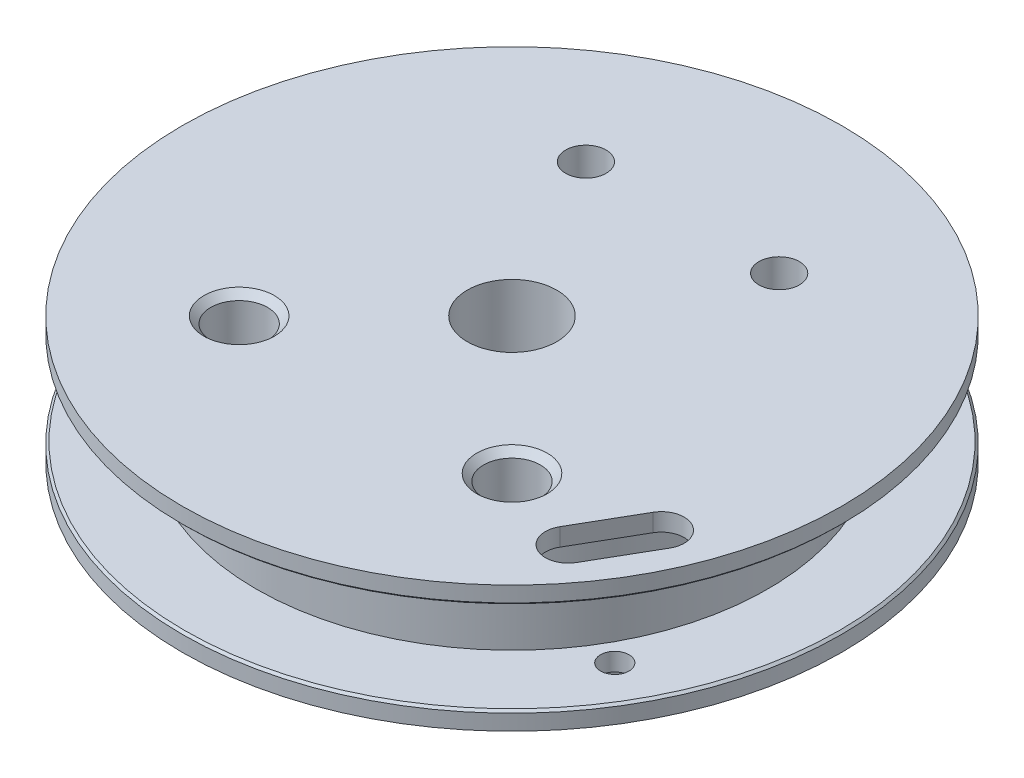
SolidWorks part; units mm, degrees
material "6061-T6 (SS)"
ref_plane "Front Plane" through (0, 0, 0) normal (0, 0, 1) x (1, 0, 0)
ref_plane "Top Plane" through (0, 0, 0) normal (0, 1, 0) x (1, 0, 0)
ref_plane "Right Plane" through (0, 0, 0) normal (1, 0, 0) x (0, 0, -1)
sketch "Sketch1" plane through (0, 0, 0) normal (0, 0, 1) x (1, 0, 0)
  line L0 (0, 0) -> (0, 83.8274) construction
  line L1 (-2.5, 22.994) -> (-9.525, 22.994)
  line L2 (-9.525, 22.994) -> (-9.525, 28.994)
  line L3 (-9.525, 28.994) -> (-18.415, 28.994)
  line L4 (-18.415, 28.994) -> (-18.415, 29.994)
  line L5 (-18.415, 29.994) -> (-14.2875, 29.994)
  line L6 (-14.2875, 29.994) -> (-14.2875, 35.074)
  line L7 (-14.2875, 35.074) -> (-2.5, 35.074) construction
  line L8 (-14.2875, 35.074) -> (-18.415, 35.074)
  line L9 (-2.5, 35.074) -> (-2.5, 22.994)
  line L10 (-18.415, 35.074) -> (-18.415, 36.0646)
  line L11 (-18.415, 36.0646) -> (-2.5, 36.0646)
  line L12 (-2.5, 36.0646) -> (-2.5, 35.074)
  dimension "D1" = 18.415
  dimension "D2" = 5.08
  dimension "D3" = 1
  dimension "D4" = 6
  dimension "D5" = 2.5
  dimension "D6" = 9.525
  dimension "D7" = 14.2875
  dimension "D8" = 0.9906
  dimension "D9" = 18.415
revolve "Revolve1" add sketch "Sketch1" angle 360 about L0
sketch "Sketch7" plane through (0, 29.994, 0) normal (0, 1, 0) x (1, 0, 0)
  line L0 (0, 0) -> (23.0958, 0) construction
  line L1 (0, 0) -> (19.9688, -11.529) construction
  circle A1 centre (0, 0) radius 15.6845 construction
  circle A4 centre (13.5832, -7.8423) radius 0.7938
  dimension "D1" = 30
  dimension "D2" = 31.369
  dimension "D4" = 1.5875
extrude "Cut-Extrude2" cut sketch "Sketch7" against normal blind 2.54 contours A4 region at (13.5832, 29.994, 7.8423)
sketch "Sketch8" plane through (0, 36.0646, 0) normal (0, 1, 0) x (1, 0, 0)
  line L1 (-26.9486, 0) -> (27.9762, 0) construction
  line L3 (-26.9486, -7.62) -> (27.9762, -7.62) construction
  line L4 (0, 11.7169) -> (0, -23.0173) construction
  circle A0 centre (7.62, -7.62) radius 1.5748
  circle A1 centre (-7.62, -7.62) radius 1.5748
  dimension "D3" = 3.1496
  dimension "D4" = 3.1496
  dimension "D1" = 7.62
  dimension "D2" = 7.62
  dimension "D5" = 7.62
hole_wizard "1/8 (0.125) Diameter Hole1" positions "Sketch10" profile "Sketch9" hole size "1/8" standard "ANSI Inch"
sketch "Sketch10" plane through (0, 36.0646, 0) normal (0, 1, 0) x (1, 0, 0)
  point P0 (-7.62, -7.62)
  point P3 (7.62, -7.62)
sketch "Sketch9" plane through (-7.62, 36.0646, 7.62) normal (1, 0, 0) x (0, 0, 1)
  line L0 (0, 0) -> (0, 6.0339)
  line L1 (0, 6.0339) -> (1.5875, 5.08)
  line L2 (1.5875, 5.08) -> (1.5875, 0)
  line L5 (1.5875, 0) -> (0, 0)
  line L10 (0, 6.0339) -> (-1.5875, 5.08) construction
  line L11 (0, -6.35) -> (0, 107.95) construction
  dimension "Hole Dia." = 3.175
  dimension "Hole Depth" = 5.08
  dimension "Drill Angle" = 118
sketch "Sketch11" plane through (0, 36.0646, 0) normal (0, 1, 0) x (1, 0, 0)
  line L0 (-23.3463, 9.525) -> (25.6827, 9.525) construction
  line L3 (0, 0) -> (25.6827, 0) construction
  line L4 (0, 0) -> (0, 27.381) construction
  circle A0 centre (-5.3975, 9.525) radius 0.5186
  circle A1 centre (5.3975, 9.525) radius 0.4714
  dimension "D1" = 9.525
  dimension "D2" = 5.3975
  dimension "D3" = 5.3975
  dimension "D4" = 10.795
hole_wizard "#4-40 Tapped Hole1" positions "Sketch13" profile "Sketch12" tap size "#4-40" standard "ANSI Inch"
sketch "Sketch13" plane through (0, 36.0646, 0) normal (0, 1, 0) x (1, 0, 0)
  point P0 (5.3975, 9.525)
  point P3 (-5.3975, 9.525)
sketch "Sketch12" plane through (5.3975, 36.0646, -9.525) normal (1, 0, 0) x (0, 0, 1)
  line L0 (0, 0) -> (0, 6.3942)
  line L1 (0, 6.3942) -> (1.1303, 5.715)
  line L2 (1.1303, 5.715) -> (1.1303, 0)
  line L5 (1.1303, 0) -> (0, 0)
  line L10 (0, 6.3942) -> (-1.1303, 5.715) construction
  line L11 (0, -6.35) -> (0, 107.95) construction
  dimension "Tap Drill Dia." = 2.2606
  dimension "Tap Drill Depth" = 5.715
  dimension "Drill Angle" = 118
cosmetic thread "Hole Thread1"
cosmetic thread "Hole Thread2"
sketch "Sketch14" plane through (0, 36.0646, 0) normal (0, 1, 0) x (1, 0, 0)
  line L0 (0, 0) -> (20.2887, -11.7137) construction
  line L1 (0, 0) -> (22.9589, 0) construction
  line L2 (13.5832, -7.8423) -> (22.7619, 8.0557) construction
  line L3 (20.172, 3.57) -> (13.5832, -7.8423) construction
  line L4 (13.5832, -7.8423) -> (4.6877, -23.2497) construction
  line L5 (14.5357, -6.1925) -> (12.6307, -9.492) construction
  line L6 (15.6355, -6.8275) -> (13.7305, -10.127)
  line L7 (13.4358, -5.5575) -> (11.5308, -8.857)
  circle A0 centre (0, 0) radius 15.6845 construction
  circle A1 centre (13.5832, -7.8423) radius 1.5875 construction
  arc A2 (15.6355, -6.8275) -> (13.4358, -5.5575) centre (14.5357, -6.1925) ccw
  arc A3 (11.5308, -8.857) -> (13.7305, -10.127) centre (12.6307, -9.492) ccw
  point P12 (13.5832, -7.8423)
  dimension "D2" = 31.369
  dimension "D3" = 1.905
  dimension "D1" = 30
  dimension "D4" = 90
  dimension "D5" = 2.54
  dimension "D6" = 1.905
extrude "Cut-Extrude4" cut sketch "Sketch14" against normal up to next
chamfer "Chamfer1" distance 0.127 angle 45 2 edges at (0, 35.074, -18.415) (0, 29.994, -18.415)
chamfer "Chamfer2" distance 0.381 angle 45 2 edges at (7.62, 36.0646, 9.2075) (-7.62, 36.0646, 9.2075) tangent propagation no
sketch "Sketch16" plane through (0, 0, 0) normal (0, 1, 0) x (1, 0, 0)
  line L0 (13.5832, -7.8423) -> (0, 0) construction
  line L2 (0, 0) -> (15.4584, 33.1508)
  dimension "D1" = 95
ref_plane "Plane3" through (0, 0, 0) normal (0.9063, 0, 0.4226) x (0.4226, 0, -0.9063)
sketch "Sketch2" plane through (0, 0, 0) normal (0, 0, 1) x (1, 0, 0)
  line L0 (-9.525, 22.994) -> (9.525, 22.994) construction
  circle A0 centre (0, 25.994) radius 0.635
  dimension "D1" = 3
  dimension "D2" = 1.27
extrude "Cut-Extrude1" cut sketch "Sketch2" along normal up to next contours A0
hole_wizard "#10-32 Tapped Hole1" positions "Sketch20" profile "Sketch19" tap size "#10-32" standard "ANSI Inch" end condition through all
sketch "Sketch20" plane through (0, 0, 0) normal (0, 0, 1) x (1, 0, 0)
  point P0 (0, 25.994)
sketch "Sketch19" plane through (0, 25.994, 0) normal (1, 0, 0) x (0, 1, 0)
  line L0 (0, 0) -> (0, 18.415)
  line L1 (0, 18.415) -> (2.0193, 18.415)
  line L2 (2.0193, 18.415) -> (2.0193, 0)
  line L5 (2.0193, 0) -> (0, 0)
  line L11 (0, -6.35) -> (0, 107.95) construction
  dimension "Thru Tap Drill Dia." = 4.0386
  dimension "Thru Tap Drill Depth" = 18.415
cosmetic thread "Hole Thread4"
